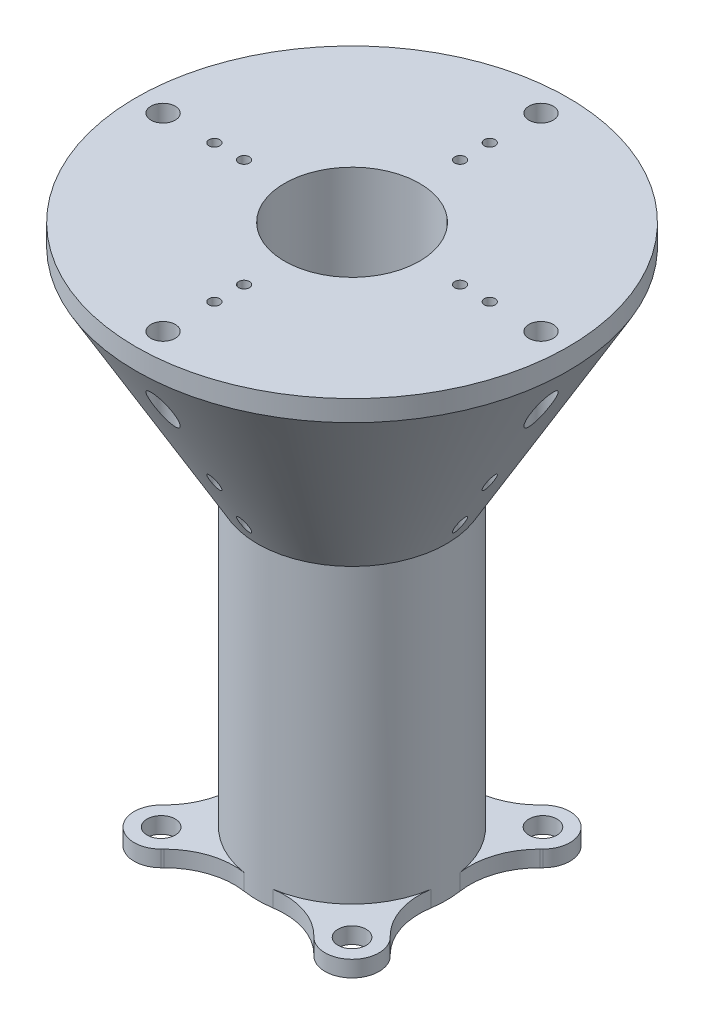
SolidWorks part; units mm, degrees
ref_plane "前视基准面" through (0, 0, 0) normal (0, 0, 1) x (1, 0, 0)
ref_plane "上视基准面" through (0, 0, 0) normal (0, 1, 0) x (1, 0, 0)
ref_plane "右视基准面" through (0, 0, 0) normal (1, 0, 0) x (0, 0, -1)
other "Configuration Table"
sketch "草图1" plane through (0, 0, 0) normal (0, 1, 0) x (1, 0, 0)
  circle A0 centre (0, 0) radius 17.5
  dimension "D1" = 35
extrude "拉伸-薄壁1" add sketch "草图1" along normal blind 100 thin thin type one direction reverse wall 5
sketch "草图2" plane through (0, 0, 0) normal (0, 1, 0) x (1, 0, 0)
  line L0 (0, 0) -> (-24.3469, 0) construction
  line L1 (17.6777, -17.6777) -> (-17.6777, 17.6777) construction
  line L2 (14.1421, -21.2132) -> (-21.2132, 14.1421)
  line L3 (21.2132, -14.1421) -> (-14.1421, 21.2132)
  line L4 (-17.6777, -17.6777) -> (17.6777, 17.6777) construction
  line L5 (-21.2132, -14.1421) -> (14.1421, 21.2132)
  line L6 (-14.1421, -21.2132) -> (21.2132, 14.1421)
  arc A0 (14.1421, -21.2132) -> (21.2132, -14.1421) centre (17.6777, -17.6777) ccw
  arc A1 (-14.1421, 21.2132) -> (-21.2132, 14.1421) centre (-17.6777, 17.6777) ccw
  arc A2 (-21.2132, -14.1421) -> (-14.1421, -21.2132) centre (-17.6777, -17.6777) ccw
  arc A3 (21.2132, 14.1421) -> (14.1421, 21.2132) centre (17.6777, 17.6777) ccw
  circle A4 centre (-17.6777, 17.6777) radius 2.6
  circle A5 centre (17.6777, 17.6777) radius 2.6
  circle A6 centre (-17.6777, -17.6777) radius 2.6
  circle A7 centre (17.6777, -17.6777) radius 2.6
  circle A9 centre (0, 0) radius 17.5
  circle A10 centre (0, 0) radius 17.5
  point P5 (0, 0)
  point P12 (0, 0)
  dimension "D4" = 5
  dimension "D5" = 5
  dimension "D6" = 5.2
  dimension "D1" = 45
  dimension "D2" = 50
  dimension "D3" = 50
  dimension "D7" = 0
extrude "凸台-拉伸1" add sketch "草图2" along normal blind 3 contours A10 L3 A1 L2 A4 | A10 L6 A3 L5 A5 | A10 L5 A2 L6 A6 | A10 L2 A0 L3 A7
sketch "草图3" plane through (0, 100, 0) normal (0, 1, 0) x (1, 0, 0)
  circle A0 centre (0, 0) radius 35 construction
  circle A1 centre (0, 35) radius 2.25
  circle A2 centre (0, 0) radius 40
  circle A3 centre (35, 0) radius 2.25
  circle A5 centre (0, -35) radius 2.25
  circle A9 centre (-35, 0) radius 2.25
  point P14 (0, 0)
  dimension "D1" = 80
  dimension "D2" = 70
  dimension "D4" = 4.5
  dimension "D3" = 4
extrude "凸台-拉伸2" add sketch "草图3" against normal blind 3
chamfer "倒角1" distance 23 angle 60 1 edges at (0, 97, 17.5) first distance on face at (-35, 97, 2.25)
fillet "圆角1" radius 13 8 edges at (-15.3941, 1.5, -8.323) (-15.3941, 1.5, 8.323) (-8.323, 1.5, 15.3941) (8.323, 1.5, 15.3941) (15.3941, 1.5, 8.323) (15.3941, 1.5, -8.323) (8.323, 1.5, -15.3941) (-8.323, 1.5, -15.3941)
sketch "草图4" plane through (0, 100, 0) normal (0, 1, 0) x (1, 0, 0)
  circle A0 centre (0, 0) radius 25.5 construction
  circle A1 centre (0, 0) radius 20 construction
  circle A2 centre (0, 25.5) radius 1
  circle A3 centre (0, 20) radius 1
  circle A4 centre (25.5, 0) radius 1
  circle A5 centre (20, 0) radius 1
  circle A6 centre (0, -25.5) radius 1
  circle A7 centre (0, -20) radius 1
  circle A8 centre (-25.5, 0) radius 1
  circle A9 centre (-20, 0) radius 1
  point P23 (0, 0)
  dimension "D1" = 51
  dimension "D2" = 40
  dimension "D3" = 2
  dimension "D4" = 2
  dimension "D5" = 4
extrude "切除-拉伸1" cut sketch "草图4" against normal through all
